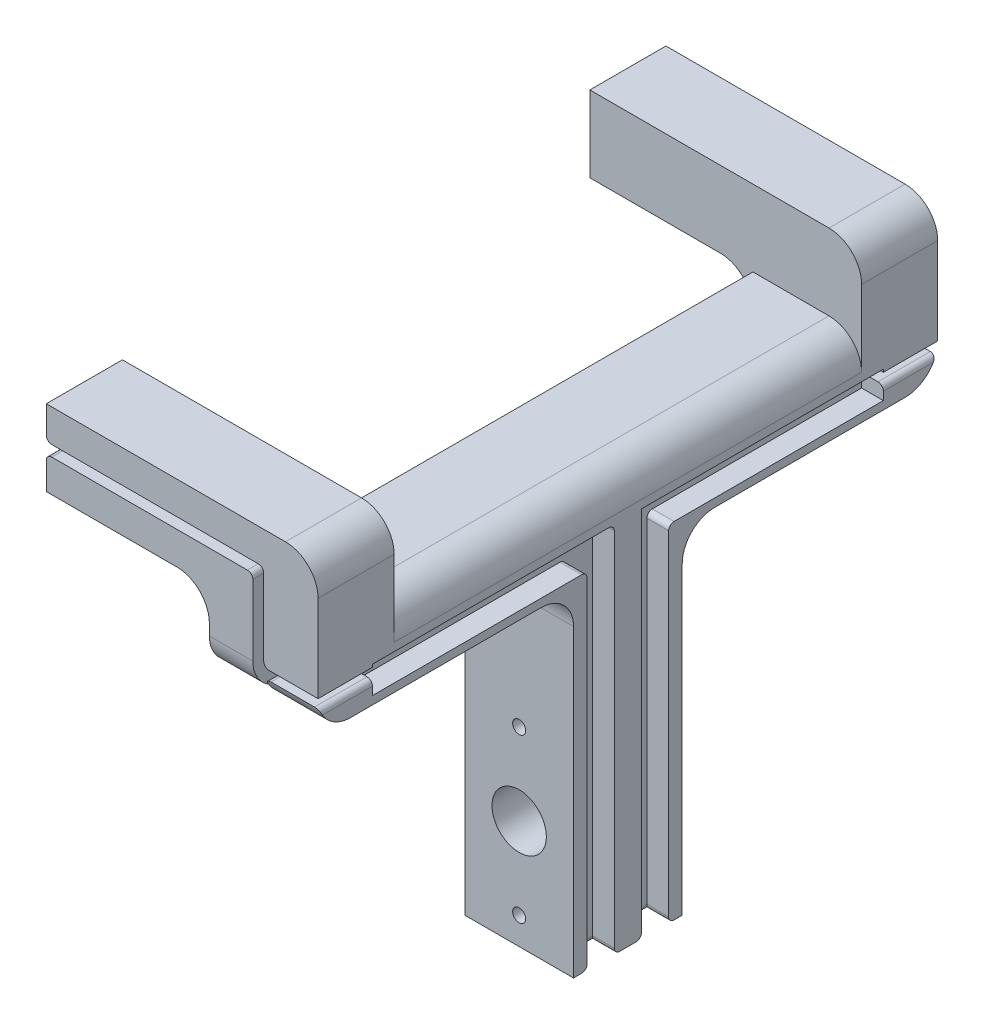
SolidWorks part; units mm, degrees
other "Marquage1"
sketch "Esquisse8" plane through (14, 100, 40) normal (0.0145, 0.0452, 0.9989) x (0.9993, 0.0332, -0.016)
ref_plane "Plan de face" through (0, 0, 0) normal (0, 0, 1) x (1, 0, 0)
ref_plane "Plan de dessus" through (0, 0, 0) normal (0, 1, 0) x (1, 0, 0)
ref_plane "Plan de droite" through (0, 0, 0) normal (1, 0, 0) x (0, 0, -1)
sketch "Esquisse1" plane through (0, 0, 0) normal (0, 0, 1) x (1, 0, 0)
  line L0 (9, 0) -> (9, 10) construction
  line L1 (0, 0) -> (18, 0) construction
  line L2 (0, 0) -> (0, 38) construction
  line L3 (0, 38) -> (18, 38) construction
  line L4 (18, 0) -> (18, 38) construction
  line L5 (9, 10) -> (0, 10) construction
  line L6 (9, 10) -> (9, 17.5) construction
  line L7 (4, 38) -> (14, 38)
  line L8 (4, 38) -> (4, 0)
  line L10 (14, 38) -> (14, 0)
  line L11 (4, 0) -> (14, 0)
  circle A1 centre (9, 10) radius 2.5
  circle A2 centre (9, 17.5) radius 0.5
  circle A4 centre (9, 2.5) radius 0.5
  circle A6 centre (16.5, 10) radius 0.5 [skipped]
  circle A7 centre (1.5, 10) radius 0.5 [skipped]
  point P24 (9, 10)
  dimension "D7" = 5
  dimension "D9" = 1
  dimension "D1" = 18
  dimension "D2" = 38
  dimension "D3" = 10
  dimension "D5" = 10
  dimension "D6" = 4
  dimension "D8" = 7.5
  dimension "D4" = 7.5
  dimension "D10" = 4
extrude "Boss.-Extru.1" add sketch "Esquisse1" along normal blind 10
sketch "Esquisse4" plane through (14, 0, 0) normal (1, 0, 0) x (0, 0, -1)
  line L0 (-26.5, 38) -> (16.5, 38)
  line L1 (16.5, 45) -> (23.5, 45)
  line L2 (23.5, 45) -> (23.5, 31)
  line L3 (23.5, 31) -> (-33.5, 31)
  line L4 (-33.5, 31) -> (-33.5, 45)
  line L5 (-33.5, 45) -> (-26.5, 45)
  line L6 (-26.5, 45) -> (-26.5, 38)
  line L8 (16.5, 38) -> (16.5, 45)
  line L9 (-5, 38) -> (-5, 0) construction
  line L10 (-10, 38) -> (0, 38) construction
  line L11 (-10, 0) -> (0, 0) construction
  point P5 (-5, 38)
  point P15 (-5, 31)
  point P17 (-30, 45)
  point P18 (20, 45)
  dimension "D1" = 50
  dimension "D2" = 7
  dimension "D3" = 7
  dimension "D4" = 45
  dimension "D5" = 45
extrude "Boss.-Extru.2" add sketch "Esquisse4" against normal blind 10
sketch "Esquisse5" plane through (4, 0, 0) normal (-1, 0, 0) x (0, 0, 1)
  line L0 (-16.5, 45) -> (-16.5, 38) construction
  line L1 (-23.5, 45) -> (-16.5, 45)
  line L2 (-23.5, 45) -> (-23.5, 38)
  line L3 (-23.5, 38) -> (-16.5, 38)
  line L4 (-16.5, 45) -> (-16.5, 38)
  line L5 (33.5, 45) -> (33.5, 31) construction
  line L6 (26.5, 45) -> (33.5, 45)
  line L7 (26.5, 45) -> (26.5, 38)
  line L8 (26.5, 38) -> (33.5, 38)
  line L9 (33.5, 45) -> (33.5, 38)
extrude "Boss.-Extru.3" add sketch "Esquisse5" along normal blind 15
fillet "Congé1" radius 3 9 edges at (4, 38, -20) (4, 38, 30) (9, 31, -23.5) (9, 31, 33.5) (14, 45, -20) (14, 45, 30) (9, 31, 0) (9, 31, 10) (14, 38, 5)
hole_wizard "Dégagement M11" positions "Esquisse6" profile "Esquisse7" hole size "M1" standard "ISO" end condition through all
sketch "Esquisse6" plane through (0, 0, 10) normal (0, 0, 1) x (1, 0, 0)
  point P0 (9, 17.5)
  point P3 (9, 2.5)
sketch "Esquisse7" plane through (9, 17.5, 10) normal (1, 0, 0) x (0, -1, 0)
  line L0 (0, 0) -> (0, 33.5)
  line L1 (0, 33.5) -> (0.6, 33.5)
  line L2 (0.6, 33.5) -> (0.6, 0)
  line L5 (0.6, 0) -> (0, 0)
  line L11 (0, -6.35) -> (0, 107.95) construction
  dimension "Diamètre du perçage jusqu'au prochain" = 1.2
  dimension "Profondeur du perçage jusqu'au prochain" = 33.5
sketch "Esquisse9" plane through (14, 0, 0) normal (1, 0, 0) x (0, 0, -1)
  line L5 (0, 0) -> (-2.5, 0)
  line L6 (0, 0) -> (0, 20)
  line L7 (0, 20) -> (-2.5, 20)
  line L8 (-2.5, 0) -> (-2.5, 20)
  dimension "D2" = 20
  dimension "D4" = 2.5
extrude "Enlèv. mat.-Extru.1" [suppressed] cut sketch "Esquisse9" against normal up to surface (10 mm away) up to face at (4, 29, 5)
sketch "Esquisse10" plane through (0, 0, 33.5) normal (0, 0, 1) x (1, 0, 0)
  line L0 (-11, 38) -> (-11, 45) construction
  line L1 (-11, 41) -> (8, 41)
  line L2 (-11, 41) -> (-11, 42)
  line L3 (-11, 42) -> (9, 42)
  line L5 (14, 31) -> (4, 31) construction
  line L7 (9, 42) -> (9, 34)
  line L9 (8, 41) -> (8, 31)
  line L10 (9, 33) -> (14, 33)
  line L12 (9, 34) -> (14, 34)
  line L13 (14, 33) -> (14, 34)
  line L16 (8, 31) -> (9, 31)
  line L17 (9, 33) -> (9, 31)
  line L18 (14, 31) -> (4, 31) construction
  point P13 (8, 31.1906)
  point P16 (-11, 41.5)
  point P17 (-11, 41.5)
  point P18 (8, 31)
  dimension "D1" = 1
  dimension "D2" = 1
  dimension "D3" = 1
  dimension "D4" = 20
extrude "Enlèv. mat.-Extru.2" cut sketch "Esquisse10" against normal blind 5
ref_plane "Plan1" through (0, 0, 5) normal (0, 0, 1) x (1, 0, 0)
sketch "Esquisse11" plane through (14, 0, 0) normal (1, 0, 0) x (0, 0, -1)
  line L0 (-10, 0) -> (0, 0) construction
  line L1 (-28.5, 34.25) -> (-6.25, 34.25)
  line L2 (-28.5, 34.25) -> (-28.5, 31.75)
  line L3 (-28.5, 31.75) -> (-8.75, 31.75)
  line L6 (-6.25, 34.25) -> (-6.25, 0)
  line L7 (-6.25, 0) -> (-8.75, 0)
  line L8 (-8.75, 31.75) -> (-8.75, 0)
  line L9 (-10, 0) -> (-10, 28) construction
  point P1 (-28.5, 33)
  point P11 (-7.5, 0)
  dimension "D1" = 2.5
  dimension "D2" = 2.5
  dimension "D3" = 2.5
extrude "Enlèv. mat.-Extru.3" cut sketch "Esquisse11" against normal blind 2
mirror "Symétrie1" about plane through (0, 0, 5) normal (0, 0, 1) of "Enlèv. mat.-Extru.3", "Enlèv. mat.-Extru.2"
fillet "Congé2" radius 0.5 25 edges at (13, 0, 8.75) (12, 0, 7.5) (13, 0, 6.25) (13, 34.25, 6.25) (13, 31.75, 8.75) (-11, 41, 31) (-11, 42, 31) (14, 33, 30.9142) (9, 34, 31) (9, 42, 31) (8, 41, 31) (-11, 41.5, 28.5) (-11, 41, -21) (-11, 41.5, -18.5) (-11, 42, -21) (9, 42, -21) (8, 41, -21) (9, 34, -21) (14, 33, -20.9142) (13, 0, 1.25) (13, 0, 3.75) (12, 0, 2.5) (13, 31.75, 1.25) (9, 33, 30.9142) (9, 33, -20.9142)
equation "\"D3@Esquisse1\"=10"
equation "\"D6@Esquisse1\"=(\"D1@Esquisse1\"-\"D5@Esquisse1\")/2"
equation "\"D8@Esquisse1\"=15/2"
